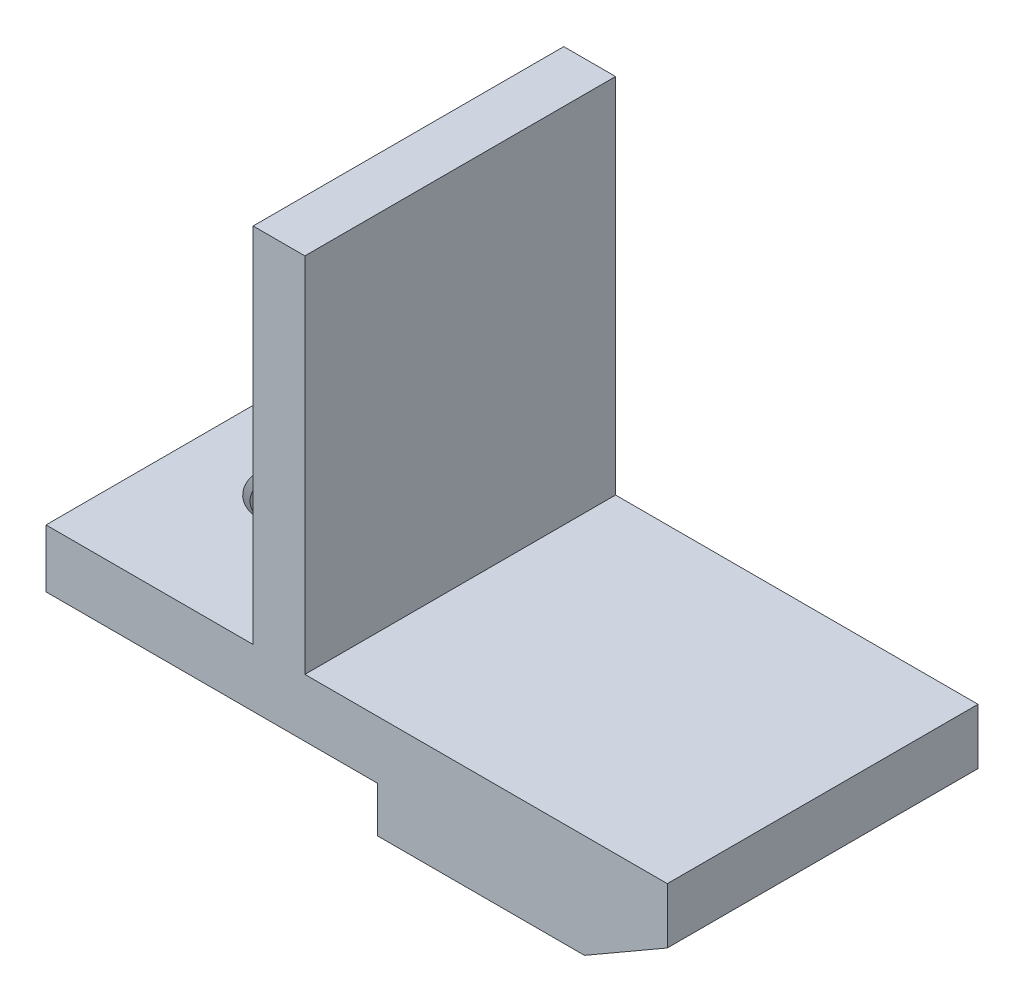
SolidWorks part; units mm, degrees
ref_plane "Front Plane" through (0, 0, 0) normal (0, 0, 1) x (1, 0, 0)
ref_plane "Top Plane" through (0, 0, 0) normal (0, 1, 0) x (1, 0, 0)
ref_plane "Right Plane" through (0, 0, 0) normal (1, 0, 0) x (0, 0, -1)
sketch "Sketch1" plane through (0, 0, 0) normal (0, 0, 1) x (1, 0, 0)
  line L0 (0, 0) -> (44.45, 0)
  line L1 (44.45, 0) -> (44.45, -12.7)
  line L2 (44.45, -12.7) -> (8.89, -12.7)
  line L3 (-31.75, -7.112) -> (-31.75, 0)
  line L4 (-31.75, 0) -> (-6.35, 0)
  line L5 (-6.35, 0) -> (-6.35, 44.45)
  line L6 (-6.35, 44.45) -> (0, 44.45)
  line L7 (0, 44.45) -> (0, 0)
  line L8 (8.89, -12.7) -> (8.89, -7.112)
  line L9 (8.89, -7.112) -> (-31.75, -7.112)
  dimension "D1" = 44.45
  dimension "D2" = 44.45
  dimension "D3" = 12.7
  dimension "D4" = 25.4
  dimension "D5" = 6.35
  dimension "D6" = 5.588
  dimension "D7" = 40.64
extrude "Boss-Extrude1" add sketch "Sketch1" along normal blind 38.1
hole_wizard "3/8 (0.375) Diameter Hole1" positions "Sketch5" profile "Sketch3" hole size "3/8" standard "ANSI Inch" end condition through all
sketch "Sketch5" plane through (0, 0, 0) normal (0, 1, 0) x (1, 0, 0)
  line L0 (-6.35, 0) -> (-31.75, 0) construction
  point P0 (-19.05, -19.05)
  point P5 (-19.05, 0)
sketch "Sketch3" plane through (-19.05, 0, 19.05) normal (1, 0, 0) x (0, 0, 1)
  line L0 (0, 0) -> (0, 12.7)
  line L1 (0, 12.7) -> (4.7625, 12.7)
  line L2 (4.7625, 12.7) -> (4.7625, 0.635)
  line L3 (4.7625, 0.635) -> (5.3975, 0)
  line L5 (5.3975, 0) -> (0, 0)
  line L6 (-4.7625, 0.635) -> (-5.3975, 0) construction
  line L11 (0, -6.35) -> (0, 107.95) construction
  dimension "Thru Hole Dia." = 9.525
  dimension "Thru Hole Depth" = 12.7
  dimension "Near C'Sink Dia." = 10.795
  dimension "Near C'Sink Angle" = 90
chamfer "Chamfer1" distance 10.16 angle 30 1 edges at (44.45, -12.7, 19.05) first distance on face at (26.67, -12.7, 19.05)
